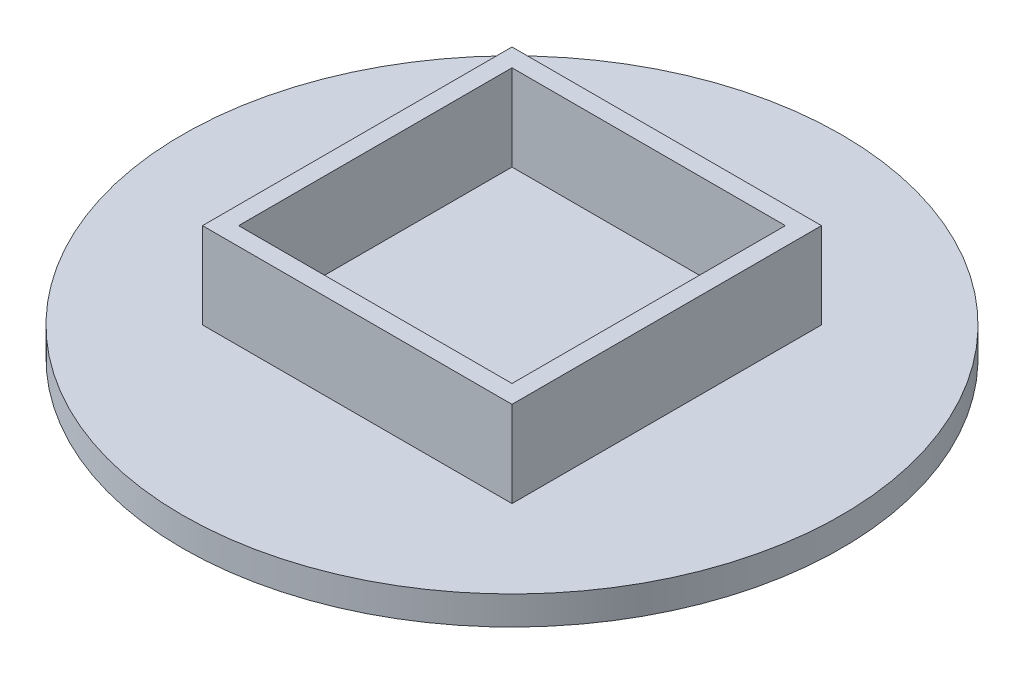
SolidWorks part; units mm, degrees
material "ABS_rapid_prototype"
ref_plane "Front" through (0, 0, 0) normal (0, 0, 1) x (1, 0, 0)
ref_plane "Top" through (0, 0, 0) normal (0, 1, 0) x (1, 0, 0)
ref_plane "Right" through (0, 0, 0) normal (1, 0, 0) x (0, 0, -1)
sketch "Sketch1" plane through (0, 0, 0) normal (0, 1, 0) x (1, 0, 0)
  line L1 (-50.8, 50.8) -> (50.8, 50.8)
  line L2 (-50.8, 50.8) -> (-50.8, -50.8)
  line L3 (-50.8, -50.8) -> (50.8, -50.8)
  line L4 (50.8, 50.8) -> (50.8, -50.8)
  line L5 (-50.8, 50.8) -> (50.8, -50.8) construction
  line L6 (-50.8, -50.8) -> (50.8, 50.8) construction
  line L7 (-38.1, 38.1) -> (38.1, 38.1)
  line L8 (-38.1, 38.1) -> (-38.1, -38.1)
  line L9 (-38.1, -38.1) -> (38.1, -38.1)
  line L10 (38.1, 38.1) -> (38.1, -38.1)
  line L11 (-38.1, 38.1) -> (38.1, -38.1) construction
  line L12 (-38.1, -38.1) -> (38.1, 38.1) construction
  line L13 (-34.29, 34.29) -> (34.29, 34.29)
  line L14 (-34.29, 34.29) -> (-34.29, -34.29)
  line L15 (-34.29, -34.29) -> (34.29, -34.29)
  line L16 (34.29, 34.29) -> (34.29, -34.29)
  line L17 (-34.29, 34.29) -> (34.29, -34.29) construction
  line L18 (-34.29, -34.29) -> (34.29, 34.29) construction
  line L19 (-30.29, 30.29) -> (30.29, 30.29)
  line L20 (-30.29, 30.29) -> (-30.29, -30.29)
  line L21 (-30.29, -30.29) -> (30.29, -30.29)
  line L22 (30.29, 30.29) -> (30.29, -30.29)
  line L23 (-30.29, 30.29) -> (30.29, -30.29) construction
  line L24 (-30.29, -30.29) -> (30.29, 30.29) construction
  point P0 (0, 0)
  point P5 (0, 0)
  point P11 (0, 0)
  point P16 (0, 0)
  dimension "D1" = 101.6
  dimension "D2" = 76.2
  dimension "D3" = 68.58
  dimension "D4" = 60.58
extrude "Boss-Extrude1" add sketch "Sketch1" along normal blind 25.4 contours L16 L13 L14 L15 L19 L22 L21 L20 region at (0, 0, -33.3201)
sketch "Sketch2" plane through (0, 0, 0) normal (0, 1, 0) x (1, 0, 0)
  line L7 (-34.29, -34.29) -> (34.29, -34.29)
  line L8 (-34.29, -34.29) -> (-34.29, 34.29)
  line L9 (-34.29, 34.29) -> (34.29, 34.29)
  line L10 (34.29, -34.29) -> (34.29, 34.29)
  circle A0 centre (0, 0) radius 73.025
  point P0 (0, 0)
  point P5 (0, 0)
  dimension "D1" = 146.05
extrude "Boss-Extrude2" add sketch "Sketch2" along normal blind 6.35 contours A0
